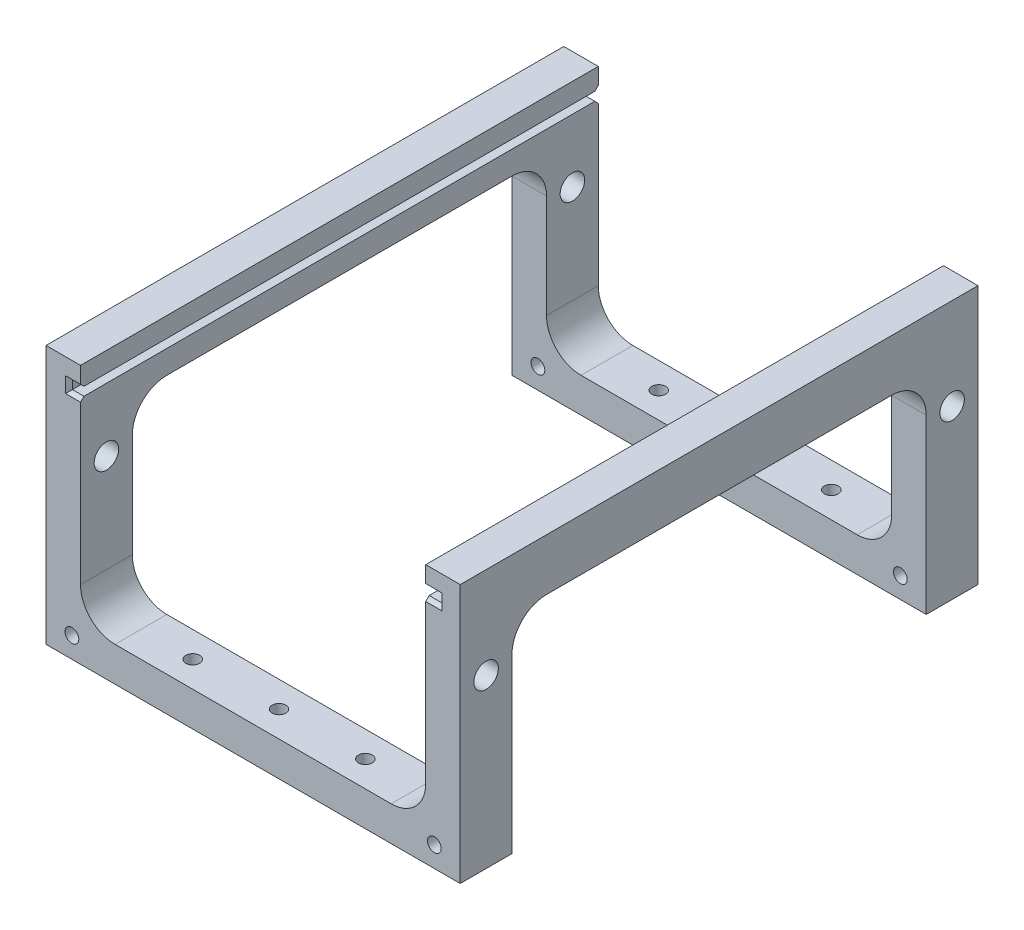
SolidWorks part; units mm, degrees
material "Commercially Pure CP-Ti UNS R50400 (SS)"
ref_plane "Front Plane" through (0, 0, 0) normal (0, 0, 1) x (1, 0, 0)
ref_plane "Top Plane" through (0, 0, 0) normal (0, 1, 0) x (1, 0, 0)
ref_plane "Right Plane" through (0, 0, 0) normal (1, 0, 0) x (0, 0, -1)
sketch "Sketch1" plane through (0, 0, 0) normal (0, 1, 0) x (1, 0, 0)
  line L1 (-60, 75) -> (60, 75)
  line L2 (-60, 75) -> (-60, -75)
  line L3 (-60, -75) -> (60, -75)
  line L4 (60, 75) -> (60, -75)
  line L5 (-60, 75) -> (60, -75) construction
  line L6 (-60, -75) -> (60, 75) construction
  point P0 (0, 0)
  dimension "D1" = 150
  dimension "D2" = 120
extrude "Boss-Extrude1" add sketch "Sketch1" along normal blind 75
sketch "Sketch3" plane through (0, 0, 75) normal (0, 0, 1) x (1, 0, 0)
  line L1 (-53.3455, 69.25) -> (53.6545, 69.25)
  line L2 (-53.3455, 69.25) -> (-53.3455, 66.75)
  line L3 (-53.3455, 66.75) -> (53.6545, 66.75)
  line L4 (53.6545, 69.25) -> (53.6545, 66.75)
  line L5 (-53.3455, 69.25) -> (53.6545, 66.75) construction
  line L6 (-53.3455, 66.75) -> (53.6545, 69.25) construction
  point P0 (0.1545, 68)
  dimension "D1" = 107
  dimension "D2" = 2.5
  dimension "D3" = 68
extrude "Cut-Extrude2" cut sketch "Sketch3" against normal through all
sketch "Sketch2" plane through (0, 75, 0) normal (0, 1, 0) x (1, 0, 0)
  line L0 (60, 75) -> (-60, 75) construction
  line L1 (-50, -75) -> (50, -75)
  line L2 (-50, -75) -> (-50, 75)
  line L3 (-50, 75) -> (50, 75)
  line L4 (50, -75) -> (50, 75)
  line L5 (-50, -75) -> (50, 75) construction
  line L6 (-50, 75) -> (50, -75) construction
  point P0 (0, 0)
  dimension "D1" = 100
extrude "Cut-Extrude1" cut sketch "Sketch2" against normal blind 65
fillet "Fillet1" radius 10 2 edges at (-50, 10, 0) (50, 10, 0)
sketch "Sketch4" plane through (0, 10, 0) normal (0, 1, 0) x (1, 0, 0)
  line L0 (40, 75) -> (-40, 75) construction
  line L1 (-40, -75) -> (40, -75) construction
  circle A0 centre (0, 67.5) radius 2
  circle A1 centre (25, 67.5) radius 2
  circle A2 centre (-25, 67.5) radius 2
  circle A3 centre (-25, -67.5) radius 2
  circle A4 centre (25, -67.5) radius 2
  circle A5 centre (0, -67.5) radius 2
  point P9 (0, 0)
  point P10 (0, 0)
  point P14 (0, 0)
  point P20 (60, 0)
  dimension "D1" = 4
  dimension "D8" = 4
  dimension "D2" = 25
  dimension "D3" = 25
  dimension "D4" = 7.5
  dimension "D5" = 25
  dimension "D6" = 25
  dimension "D7" = 7.5
extrude "Cut-Extrude3" cut sketch "Sketch4" against normal through all
sketch "Sketch5" plane through (0, 0, 75) normal (0, 0, 1) x (1, 0, 0)
  line L0 (-60, 0) -> (60, 0) construction
  circle A0 centre (-52.5, 6) radius 2
  circle A1 centre (52.5, 6) radius 2
  dimension "D2" = 4
  dimension "D1" = 6
  dimension "D3" = 52.5
  dimension "D4" = 52.5
extrude "Cut-Extrude4" cut sketch "Sketch5" against normal through all
sketch "Sketch6" plane through (60, 0, 0) normal (1, 0, 0) x (0, 0, -1)
  line L0 (-75, 0) -> (75, 0) construction
  line L2 (75, 75) -> (75, 0) construction
  line L3 (-75, 75) -> (-75, 0) construction
  circle A0 centre (67.5, 48.5) radius 3.55
  circle A1 centre (-67.5, 48.5) radius 3.55
  point P2 (0, 0)
  point P5 (0, 0)
  point P6 (0, 0)
  point P12 (-45.8917, 46.6876)
  dimension "D1" = 7.1
  dimension "D4" = 7.1
  dimension "D2" = 48.5
  dimension "D3" = 7.5
  dimension "D5" = 7.5
extrude "Cut-Extrude5" cut sketch "Sketch6" against normal through all
chamfer "Chamfer1" distance 1 angle 45 12 edges at (51.8272, 69.25, 75) (53.6545, 68, 75) (51.8272, 66.75, 75) (51.8272, 66.75, -75) (53.6545, 68, -75) (51.8272, 69.25, -75) (-51.6728, 66.75, -75) (-51.6728, 69.25, -75) (-53.3455, 68, -75) (-51.6728, 66.75, 75) (-51.6728, 69.25, 75) (-53.3455, 68, 75)
sketch "Sketch7" plane through (60, 0, 0) normal (1, 0, 0) x (0, 0, -1)
  line L0 (-60, 0) -> (60, 0)
  line L2 (-60, 0) -> (-60, 60)
  line L3 (-60, 60) -> (60, 60)
  line L4 (60, 0) -> (60, 60)
  line L5 (-75, 0) -> (75, 0) construction
  line L8 (0, 60) -> (0, 0) construction
  line L10 (60, 30) -> (-60, 30) construction
  point P0 (0, 0)
  point P11 (0, 0)
  point P12 (60, 60)
  point P15 (-60, 60)
  line M7 (-75, 0) -> (75, 0)
  dimension "D1" = 120
  dimension "D2" = 60
extrude "Cut-Extrude6" cut sketch "Sketch7" against normal through all contours L2 L4 L3 M7 region at (60, 30, 0)
fillet "Fillet2" radius 10 4 edges at (55, 60, -60) (-55, 60, -60) (-55, 60, 60) (55, 60, 60)
